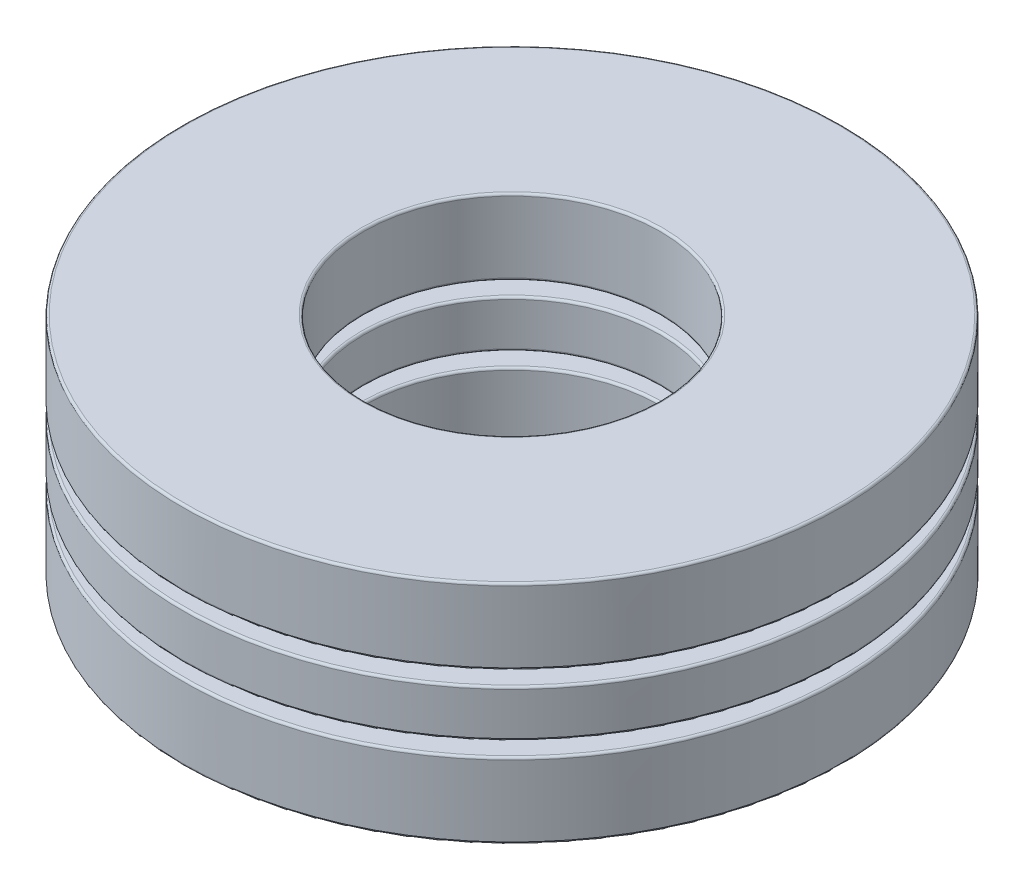
SolidWorks part; units mm, degrees
ref_plane "Front Plane" through (0, 0, 0) normal (0, 0, 1) x (1, 0, 0)
ref_plane "Top Plane" through (0, 0, 0) normal (0, 1, 0) x (1, 0, 0)
ref_plane "Right Plane" through (0, 0, 0) normal (1, 0, 0) x (0, 0, -1)
sketch "Sketch1" plane through (0, 0, 0) normal (1, 0, 0) x (0, 0, -1)
  line L0 (-7.1437, 0) -> (7.1437, 0) construction
  line L1 (0, -2.4511) -> (0, 2.4511) construction
  line L2 (-7.1437, 0.5106) -> (-3.2131, 0.5106)
  line L3 (-7.1437, 0.5106) -> (-7.1437, -0.5106)
  line L4 (-7.1437, -0.5106) -> (-3.2131, -0.5106)
  line L5 (-3.2131, 0.5106) -> (-3.2131, -0.5106)
  line L6 (-5.1784, 0.817) -> (-5.1784, -0.817) construction
  circle A0 centre (-5.1784, 0) radius 0.817 construction
  point P13 (-5.1784, 0.5106)
  dimension "D1" = 1.6341
  dimension "OD" = 14.2875
  dimension "Shaft Dia" = 6.4262
  dimension "Th" = 4.9022
  dimension "D2" = 1.0213
revolve "Revolve1" add sketch "Sketch1" angle 360 about L1
sketch "Sketch3" plane through (0, 0, 0) normal (1, 0, 0) x (0, 0, -1)
  line L0 (-5.1784, 0.817) -> (-5.1784, -0.817)
  arc A0 (-5.1784, 0.817) -> (-5.1784, -0.817) centre (-5.1784, 0) ccw
  circle A1 centre (-5.1784, 0) radius 0.817 construction
revolve "Cut-Revolve1" cut sketch "Sketch3" angle 360 about L0
sketch "Sketch2" plane through (0, 0, 0) normal (1, 0, 0) x (0, 0, -1)
  line L0 (-5.1784, 0.817) -> (-5.1784, -0.817)
  arc A0 (-5.1784, 0.817) -> (-5.1784, -0.817) centre (-5.1784, 0) ccw
  circle A2 centre (-5.1784, 0) radius 0.817 construction
revolve "Revolve2" add sketch "Sketch2" angle 360 about L0
ref_axis "Axis1" through (0, 2.4511, 0) along (0, -1, 0)
pattern_circular "CirPattern1" count 3 every 120 about axis through (0, 2.4511, 0) along (0, -1, 0) of bodies 187
pattern_circular "CirPattern2" count 3 every 120 about axis through (0, 2.4511, 0) along (0, -1, 0) of "Cut-Revolve1"
sketch "Sketch4" plane through (0, 0, 0) normal (1, 0, 0) x (0, 0, -1)
  line L0 (-7.1437, 0.5106) -> (-7.1437, -0.5106) construction
  line L1 (-7.1437, 0.817) -> (-3.2131, 0.817)
  line L2 (-7.1437, 0.817) -> (-7.1437, 2.4511)
  line L3 (-7.1437, 2.4511) -> (-3.2131, 2.4511)
  line L4 (-3.2131, 0.817) -> (-3.2131, 2.4511)
  line L5 (-7.1437, -2.4511) -> (-3.2131, -2.4511)
  line L6 (-7.1437, -2.4511) -> (-7.1437, -0.817)
  line L7 (-7.1437, -0.817) -> (-3.2131, -0.817)
  line L8 (-3.2131, -2.4511) -> (-3.2131, -0.817)
  line L9 (-5.1784, 0.817) -> (-5.1784, -0.817) construction
  line L10 (-3.2131, 0.5106) -> (-3.2131, -0.5106) construction
  line L11 (0, 0) -> (-7.1437, 0) construction
  line L12 (-7.1437, 0) -> (7.1437, 0) construction
  dimension "Ht" = 4.9022
revolve "Revolve3" add sketch "Sketch4" angle 360 about L1
fillet "Fillet1" radius 0.049 4 edges at (0, 0.817, -3.2131) (0, 2.4511, -3.2131) (0, 0.817, -7.1437) (0, 2.4511, -7.1437)
fillet "Fillet2" radius 0.049 4 edges at (0, -0.5106, -3.2131) (0, 0.5106, -3.2131) (0, -0.5106, -7.1437) (0, 0.5106, -7.1437)
fillet "Fillet3" radius 0.049 4 edges at (0, -2.4511, -3.2131) (0, -0.817, -3.2131) (0, -2.4511, -7.1437) (0, -0.817, -7.1437)
equation "\"D1@Sketch1\" = \"Th@Sketch1\"/3"
equation "\"D2@Sketch1\" = \"D1@Sketch1\"*.625"
equation "\"Balls@CirPattern1\" = \"OD@Sketch1\"*5"
equation "\"Angle@CirPattern1\" = 360/\"Balls@CirPattern1\""
equation "\"D1@CirPattern2\" = \"Balls@CirPattern1\""
equation "\"D2@CirPattern2\" = \"Angle@CirPattern1\""
equation "\"D1@Fillet1\" = \"Th@Sketch1\"*.01"
equation "\"D1@Fillet2\" = \"D1@Fillet1\""
equation "\"D1@Fillet3\" = \"D1@Fillet1\""
